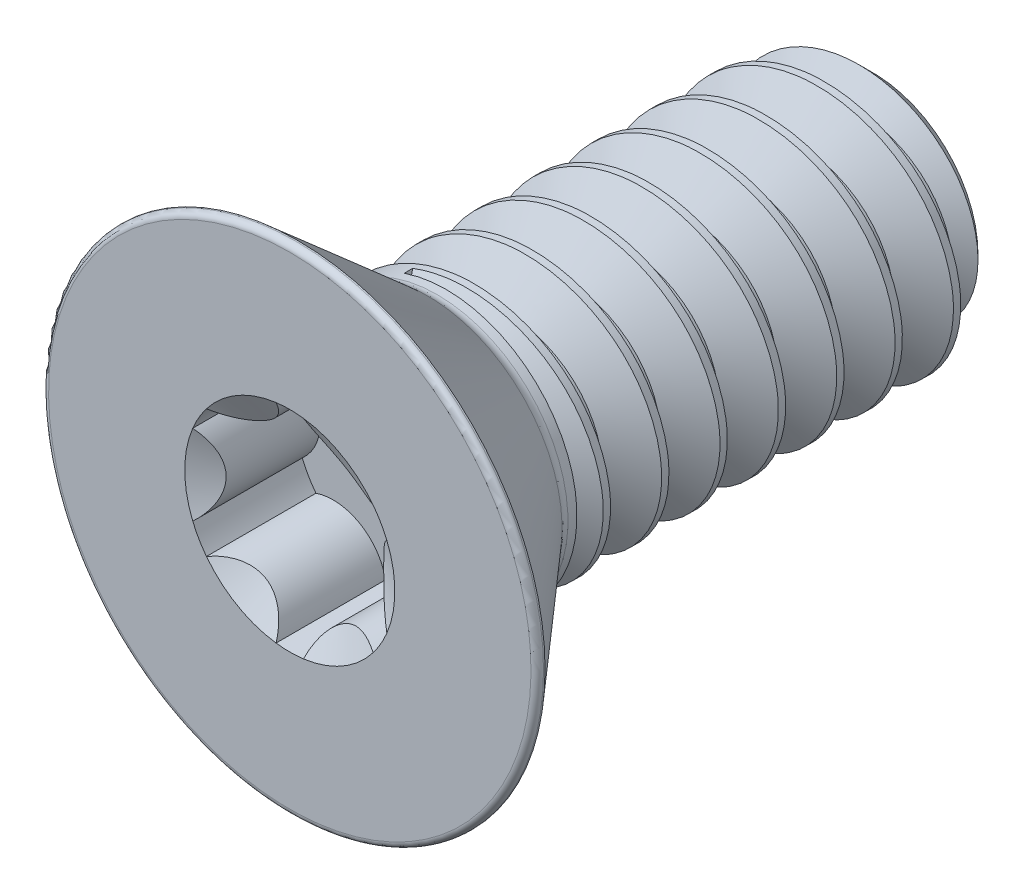
SolidWorks part; units mm, degrees
ref_plane "Front" through (0, 0, 0) normal (0, 0, 1) x (1, 0, 0)
ref_plane "Top" through (0, 0, 0) normal (0, 1, 0) x (1, 0, 0)
ref_plane "Right" through (0, 0, 0) normal (1, 0, 0) x (0, 0, -1)
sketch "Sketch1" plane through (0, 0, 0) normal (1, 0, 0) x (0, 0, -1)
  line L0 (-3.175, 2.6924) -> (-1.4732, 2.6924) construction
  line L2 (-3.175, 0) -> (3.175, 0) construction
  line L4 (3.175, 1.4224) -> (-1.4732, 1.4224) construction
  line L5 (-3.175, 0) -> (-3.175, 2.6924) construction
  line L6 (-3.175, 2.6924) -> (-3.175, -2.6924) construction
  line L7 (3.175, 1.4224) -> (3.175, -1.4224) construction
  line L8 (-3.175, -2.6924) -> (-1.4732, -2.6924) construction
  line L9 (-2.9342, 2.6924) -> (0.1631, 0) construction
  line L11 (3.175, -1.4224) -> (-1.4732, -1.4224) construction
  line L13 (-2.9342, 2.6924) -> (-2.9342, -2.6924) construction
  line L14 (-2.9342, -2.6924) -> (0.1631, 0) construction
  line L15 (-1.4732, 2.6924) -> (-1.4732, 1.4224) construction
  line L16 (3.175, 1.4224) -> (3.81, 1.4224) construction
  line L17 (-3.175, 1.143) -> (-3.175, -1.143) construction
  point P5 (-2.9342, 2.6924)
  point P10 (0, 0)
  point P17 (1.5875, -1.4224)
  point P23 (-2.9342, 0)
  point P24 (-3.175, 0)
  dimension "Head Diameter" = 5.3848
  dimension "Thread Size" = 2.8448
  dimension "Head Height" = 1.7018
  dimension "Length" = 6.35
  dimension "Countersink Angle" = 82
  dimension "Thread Pitch" = 0.635
  dimension "D1" = 1.5875
  dimension "Torx Diameter" = 2.286
sketch "Sketch12" plane through (0, 0, 0) normal (1, 0, 0) x (0, 0, -1)
  line L0 (-3.175, 0) -> (3.175, 0)
  line L1 (3.175, 0) -> (3.175, 1.4224)
  line L2 (3.175, 1.4224) -> (-1.6289, 1.4224)
  line L5 (-3.175, 2.6924) -> (-3.175, 0)
  line L6 (-1.4732, 2.6924) -> (-1.4732, 1.4224) construction
  line L7 (-3.175, 2.6924) -> (-3.0899, 2.6924)
  line L8 (-3.175, 2.6924) -> (-1.4732, 2.6924) construction
  line L9 (-3.0899, 2.6924) -> (-1.6289, 1.4224)
  line L10 (-2.9342, 2.6924) -> (0.1631, 0) construction
  line L14 (-3.0899, -2.6924) -> (-1.6289, -1.4224) construction
  dimension "D1" = 0.0851
  dimension "D2" = 0.1557
revolve "Revolve3" add sketch "Sketch12" angle 360 about L0
chamfer "Chamfer1" distance 0.2845 angle 45 1 edges at (0, -1.4224, -3.175)
sketch "Sketch5" plane through (0, 0, 3.175) normal (0, 0, 1) x (1, 0, 0)
  line L0 (0, 0) -> (-1.143, 0) construction
  line L1 (0, 0) -> (-0.9899, 0.5715) construction
  line L2 (0, 0) -> (-0.9899, -0.5715) construction
  line L3 (-0.9899, -0.5715) -> (0, 0)
  line L4 (0, 0) -> (-0.9899, 0.5715)
  line L5 (0, 0) -> (-1.056, -0.4374) construction
  line L6 (0, 1.143) -> (0, 1.0001) construction
  line L7 (0, 1.0001) -> (0, 0.8573) construction
  line L8 (0, 0) -> (0, -0.8573) construction
  line L9 (0, 0) -> (0.4286, -0.7424) construction
  circle A0 centre (0, 0) radius 1.143 construction
  circle A1 centre (0, 0) radius 1.0001 construction
  circle A2 centre (0, 0) radius 0.8573 construction
  arc A4 (-1.056, -0.4374) -> (-1.056, 0.4374) centre (-1.438, 0) ccw
  arc A5 (-1.056, 0.4374) -> (-0.9899, 0.5715) centre (0, 0) cw
  arc A6 (-1.056, -0.4374) -> (-0.9899, -0.5715) centre (0, 0) ccw
  point P13 (0, -0.8573)
  point P19 (0.4286, -0.7424)
  dimension "D3" = 1.7145
  dimension "D4" = 30
  dimension "D5" = 30
  dimension "D1" = 7.5
  dimension "D2" = 30
extrude "Cut-Extrude2" cut sketch "Sketch5" against normal blind 1.1913
pattern_circular "CirPattern1" count 6 over 360 about axis through (0, 0, 3.175) along (0, 0, -1) of "Cut-Extrude2"
sketch "Sketch6" plane through (0, 0, 3.175) normal (0, 0, 1) x (1, 0, 0)
  circle A0 centre (0, 0) radius 1.143
extrude "Cut-Extrude3" cut sketch "Sketch6" against normal blind 1.1913 draft 60
fillet "Fillet1" radius 0.0681 1 edges at (0, -2.6924, 3.175)
fillet "Fillet2" radius 0.1557 1 edges at (0, -1.4224, 1.6289)
ref_plane "Plane1" through (0, 0, 1.4732) normal (0, 0, 1) x (1, 0, 0)
split "Split1" trim tools "Plane1" bodies to split 113 resulting bodies 132 133
sketch "Sketch13" plane through (0, 0, -3.175) normal (0, 0, -1) x (-1, 0, 0)
  circle A0 centre (0, 0) radius 1.4224
curve "Helix/Spiral1" pitch 0.635 height 5.113 radius 1.4224 centre (0, 0, -3.175) axis (0, 0, 1) start towards (0, 1, 0)
sketch "Sketch14" plane through (0, 0, 0) normal (1, 0, 0) x (0, 0, -1)
  line L0 (3.1353, 1.4911) -> (3.7703, 1.4911) construction
  line L1 (3.7703, 1.4911) -> (3.4528, 0.9412) construction
  line L2 (3.4528, 0.9412) -> (3.1353, 1.4911) construction
  line L3 (3.4528, 0.9412) -> (3.4528, 1.01) construction
  line L4 (3.4528, 1.01) -> (3.4528, 1.4224) construction
  line L5 (3.4528, 1.4224) -> (3.4528, 1.4911) construction
  line L6 (3.175, 1.4224) -> (3.7306, 1.4224) construction
  line L8 (3.1552, 1.4568) -> (3.7505, 1.4568) construction
  line L9 (3.4131, 1.01) -> (3.4925, 1.01)
  line L10 (3.4131, 1.01) -> (3.4925, 1.01) construction
  line L11 (3.4925, 1.01) -> (3.7505, 1.4568)
  line L12 (3.7505, 1.4568) -> (3.1552, 1.4568)
  line L13 (3.1552, 1.4568) -> (3.4131, 1.01)
  point P8 (3.4528, 1.4224)
  point P13 (3.4528, 1.01)
  point P15 (3.4528, 1.4568)
  point P16 (3.4528, 1.4568)
  dimension "D1" = 0.635
  dimension "D2" = 0.0794
sweep "Cut-Sweep2" cut profiles "Sketch14" path "Helix/Spiral1" align with end faces yes
sketch "Sketch15" plane through (0, 0, 1.4732) normal (0, 0, 1) x (1, 0, 0)
  line L0 (0, 0) -> (0, 2.6924) construction
  circle A0 centre (0, 0) radius 1.4224
  point P3 (0, 1.4224)
  dimension "D1" = 0
extrude "Boss-Extrude1" add sketch "Sketch15" against normal through all draft 60
equation "\"D1@Cut-Extrude2\" = \"Head Height@Sketch1\" * .7"
equation "\"D1@Cut-Extrude3\" = \"D1@Cut-Extrude2\""
equation "\"Torx Dia@Sketch5\"=\"Torx Diameter@Sketch1\""
equation "\"D3@Sketch5\" = \"Torx Dia@Sketch5\" * .75"
equation "\"D3@Helix/Spiral1\" =  ( \"Length@Sketch1\" - \"Head Height@Sketch1\" )  * 1.1"
equation "\"D4@Helix/Spiral1\" = \"Thread Pitch@Sketch1\""
equation "\"D1@Sketch14\" = \"Thread Pitch@Sketch1\""
equation "\"D2@Sketch14\"=\"D1@Sketch14\"/8"
equation "\"D1@Sketch1\" = \"Thread Pitch@Sketch1\" * 2.5"
equation "\"D1@Sketch12\"=\"Head Height@Sketch1\"*.05"
equation "\"D1@Chamfer1\"=\"Thread Size@Sketch1\"*.1"
equation "\"D1@Fillet1\"=\"Head Height@Sketch1\"*.04"
equation "\"D1@Fillet2\"=\"D2@Sketch12\""
